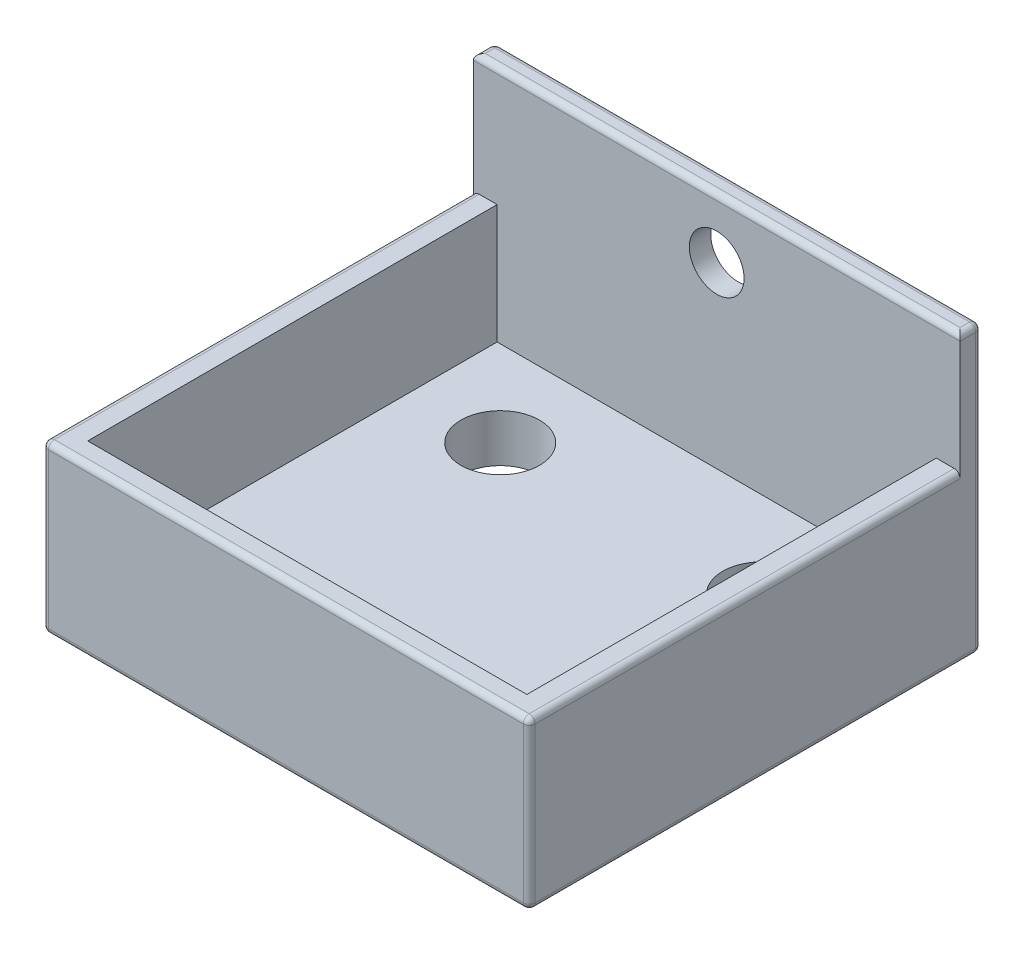
SolidWorks part; units mm, degrees
ref_plane "Front Plane" through (0, 0, 0) normal (0, 0, 1) x (1, 0, 0)
ref_plane "Top Plane" through (0, 0, 0) normal (0, 1, 0) x (1, 0, 0)
ref_plane "Right Plane" through (0, 0, 0) normal (1, 0, 0) x (0, 0, -1)
sketch "Sketch2" plane through (0, 0, 0) normal (0, 1, 0) x (1, 0, 0)
  line L1 (10.225, -9.5) -> (-10.225, -9.5)
  line L2 (10.225, -9.5) -> (10.225, 9.5)
  line L3 (10.225, 9.5) -> (-10.225, 9.5)
  line L4 (-10.225, -9.5) -> (-10.225, 9.5)
  line L5 (10.225, -9.5) -> (-10.225, 9.5) construction
  line L6 (10.225, 9.5) -> (-10.225, -9.5) construction
  point P0 (0, 0)
  dimension "D1" = 19
  dimension "D2" = 20.45
extrude "Boss-Extrude1" add sketch "Sketch2" along normal blind 7
sketch "Sketch3" plane through (0, 7, 0) normal (0, 1, 0) x (1, 0, 0)
  line L0 (10.225, -9.5) -> (10.225, 9.5) construction
  line L1 (-9.225, -8.6) -> (9.225, -8.6)
  line L2 (-9.225, -8.6) -> (-9.225, 8.6)
  line L3 (-9.225, 8.6) -> (9.225, 8.6)
  line L4 (9.225, -8.6) -> (9.225, 8.6)
  line L5 (-9.225, -8.6) -> (9.225, 8.6) construction
  line L6 (-9.225, 8.6) -> (9.225, -8.6) construction
  point P0 (0, 0)
  dimension "D1" = 18.45
  dimension "D2" = 17.2
extrude "Cut-Extrude1" cut sketch "Sketch3" against normal blind 5
sketch "Sketch7" plane through (0, 2, 0) normal (0, 1, 0) x (1, 0, 0)
  line L1 (-8.125, -7.5) -> (8.125, -7.5)
  line L2 (-8.125, -7.5) -> (-8.125, 7.5)
  line L3 (-8.125, 7.5) -> (8.125, 7.5)
  line L4 (8.125, -7.5) -> (8.125, 7.5)
  line L5 (-8.125, -7.5) -> (8.125, 7.5) construction
  line L6 (-8.125, 7.5) -> (8.125, -7.5) construction
  circle A0 centre (-5.495, 5) radius 1.65
  circle A1 centre (5.505, 5) radius 1.65
  point P0 (0, 0)
  dimension "D5" = 3.3
  dimension "D8" = 3.3
  dimension "D1" = 16.25
  dimension "D2" = 15
  dimension "D3" = 2.5
  dimension "D4" = 2.63
  dimension "D6" = 11
  dimension "D7" = 2.5
extrude "Cut-Extrude2" cut sketch "Sketch7" against normal up to surface (2 mm away) contours A0 | A1 up to face at (0, 0, 0)
sketch "Sketch13" plane through (0, 2, 0) normal (0, 1, 0) x (1, 0, 0)
  line L0 (-5.495, 5) -> (-5.495, -4) construction
  line L1 (9.225, -8.6) -> (9.225, 8.6) construction
  line L2 (-8, -4) -> (8, -4)
  line L3 (-8, -4) -> (-8, -6)
  line L4 (-8, -6) -> (8, -6)
  line L5 (8, -4) -> (8, -6)
  line L6 (-8, -4) -> (8, -6) construction
  line L7 (-8, -6) -> (8, -4) construction
  dimension "D2" = 2
  dimension "D1" = 9
  dimension "D3" = 1.225
  dimension "D4" = 16
extrude "Cut-Extrude4" cut sketch "Sketch13" against normal up to surface (2 mm away) contours L3 L2 L5 L4 up to face at (-5.495, 0, -3.35)
sketch "Sketch15" plane through (0, 7, 0) normal (0, 1, 0) x (1, 0, 0)
  line L0 (10.225, -9.5) -> (10.225, 9.5) construction
  line L1 (-10.225, 9.5) -> (10.225, 9.5)
  line L2 (-10.225, 9.5) -> (-10.225, 8.6)
  line L3 (-10.225, 8.6) -> (10.225, 8.6)
  line L4 (10.225, 9.5) -> (10.225, 8.6)
  dimension "D1" = 0.9
extrude "Boss-Extrude2" add sketch "Sketch15" along normal blind 5
sketch "Sketch16" plane through (0, 0, -8.6) normal (0, 0, 1) x (1, 0, 0)
  line L0 (0, 12) -> (0, 9.5) construction
  line L1 (-10.225, 12) -> (10.225, 12) construction
  circle A0 centre (0, 9.5) radius 1.15
  dimension "D1" = 2.3
  dimension "D2" = 2.5
extrude "Cut-Extrude5" cut sketch "Sketch16" against normal up to surface (0.9 mm away) contours A0 up to face at (0, 6, -9.5)
fillet "Fillet2" radius 0.25 15 edges at (10.225, 7, 0.45) (0, 0, -9.5) (-10.225, 6, -9.5) (-10.225, 0, 0) (-10.225, 7, 0.45) (0, 7, 9.5) (0, 0, 9.5) (10.225, 0, 0) (10.225, 6, -9.5) (10.225, 3.5, 9.5) (-10.225, 3.5, 9.5) (-10.225, 12, -9.05) (10.225, 12, -9.05) (0, 12, -9.5) (0, 12, -8.6)
